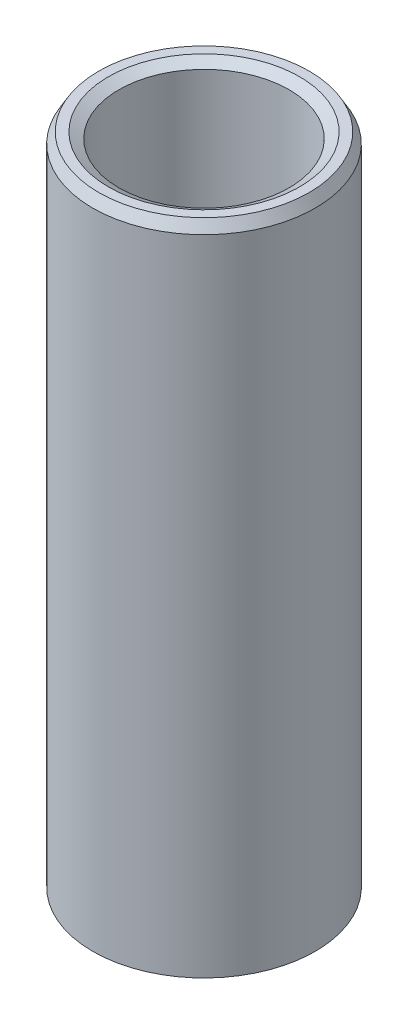
SolidWorks part; units mm, degrees
ref_plane "Front Plane" through (0, 0, 0) normal (0, 0, 1) x (1, 0, 0)
ref_plane "Top Plane" through (0, 0, 0) normal (0, 1, 0) x (1, 0, 0)
ref_plane "Right Plane" through (0, 0, 0) normal (1, 0, 0) x (0, 0, -1)
sketch "Sketch1" plane through (0, 0, 0) normal (0, 1, 0) x (1, 0, 0)
  circle A0 centre (0, 0) radius 37.5
  dimension "SLEEVE_OD" = 75
extrude "Boss-Extrude1" add sketch "Sketch1" along normal blind 222.5113
sketch "Sketch2" plane through (0, 0, 0) normal (0, 1, 0) x (1, 0, 0)
  circle A0 centre (0, 0) radius 28.6741
  dimension "BORE_D" = 57.3483
extrude "Cut-Extrude1" cut sketch "Sketch2" along normal through all
chamfer "Chamfer1" distance 3.5276 angle 30 4 edges at (0, 222.5113, 28.6741) (0, 0, 28.6741) (0, 0, 37.5) (0, 222.5113, 37.5) first distance on face at (0, 222.5113, 28.6741) first distance on face at (0, 0, 28.6741) first distance on face at (0, 222.5113, 37.5)
